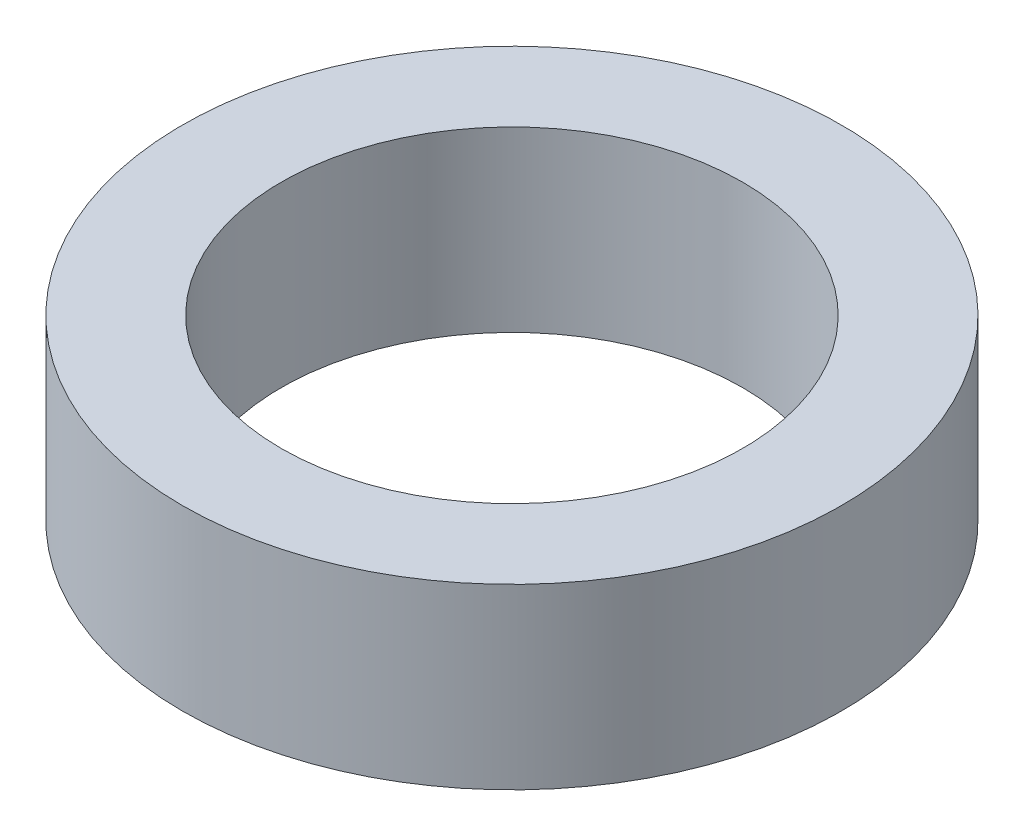
SolidWorks part; units mm, degrees
ref_plane "Front Plane" through (0, 0, 0) normal (0, 0, 1) x (1, 0, 0)
ref_plane "Top Plane" through (0, 0, 0) normal (0, 1, 0) x (1, 0, 0)
ref_plane "Right Plane" through (0, 0, 0) normal (1, 0, 0) x (0, 0, -1)
sketch "Sketch1" plane through (0, 0, 0) normal (0, 1, 0) x (1, 0, 0)
  circle A0 centre (0, 0) radius 50
  dimension "FLANGE_OD" = 100
extrude "Boss-Extrude1" add sketch "Sketch1" along normal blind 27
sketch "Sketch2" plane through (0, 0, 0) normal (0, 1, 0) x (1, 0, 0)
  circle A0 centre (0, 0) radius 35
  dimension "BORE_D" = 70
extrude "Cut-Extrude1" cut sketch "Sketch2" along normal through all
sketch "Sketch3" plane through (0, 27, 0) normal (0, 1, 0) x (1, 0, 0)
  circle A0 centre (0, 0) radius 22.0131 construction
  circle A1 centre (-22.0131, 0) radius 2.3972
  dimension "BOLT_D" = 4.7945
  dimension "BOLT_PCD" = 44.0263
extrude "Cut-Extrude2" cut sketch "Sketch3" against normal blind 22.3802 rebuild error yes
pattern_circular "CirPattern1" count 3 over 360 rebuild error yes
